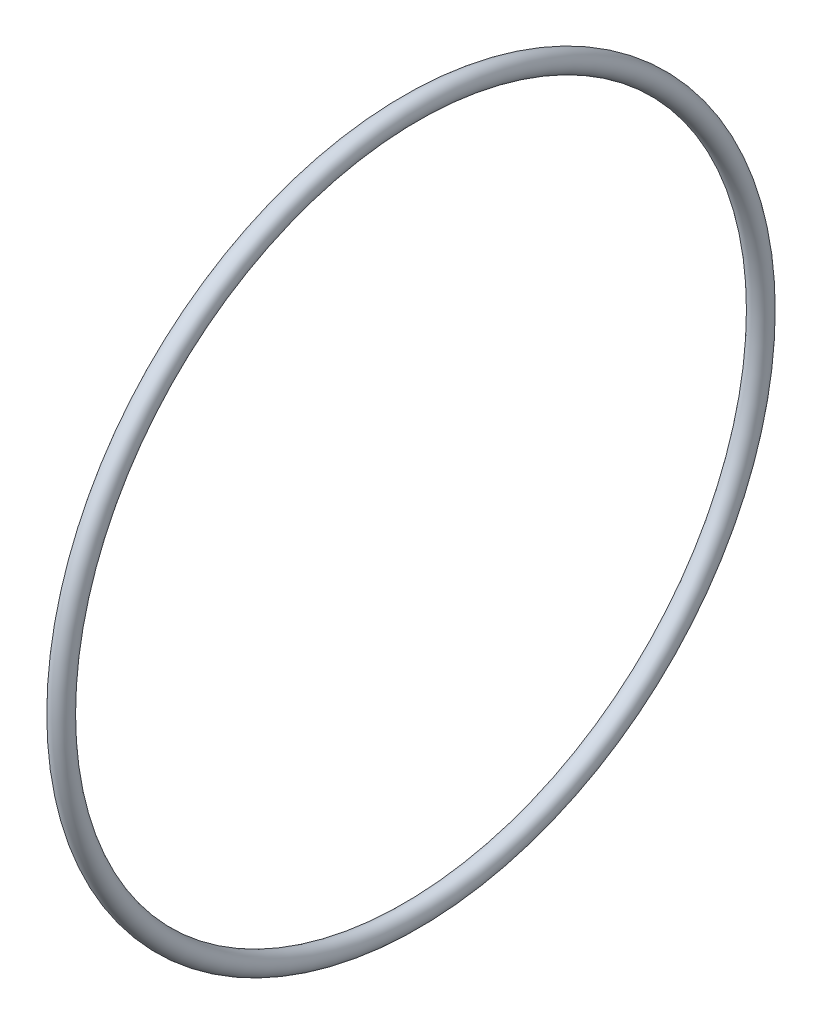
SolidWorks part; units mm, degrees
ref_plane "Front Plane" through (0, 0, 0) normal (0, 0, 1) x (1, 0, 0)
ref_plane "Top Plane" through (0, 0, 0) normal (0, 1, 0) x (1, 0, 0)
ref_plane "Right Plane" through (0, 0, 0) normal (1, 0, 0) x (0, 0, -1)
sketch "Sketch2" plane through (0, 0, 0) normal (0, 0, 1) x (1, 0, 0)
  line L0 (0, 0) -> (58.591, 0) construction
  line L2 (0, 0) -> (18.4, 0)
  line L3 (0, 0) -> (0, 2.5)
  line L4 (0, 2.5) -> (18.4, 2.5)
  line L5 (18.4, 0) -> (18.4, 2.5)
  line L6 (6.0094, 2.5) -> (6.0094, 6)
  line L11 (6.0094, 6) -> (9.9794, 6)
  line L16 (12.9794, 6) -> (12.9794, 3)
  line L17 (12.9794, 3) -> (13.6398, 3)
  line L18 (13.6398, 3) -> (13.6398, 2.5)
  line L19 (13.6398, 2.5) -> (6.0094, 2.5)
  line L22 (13.6398, 2.5) -> (16.1198, 2.5)
  line L23 (13.6398, 2.5) -> (13.6398, 4)
  line L24 (13.6398, 4) -> (16.1198, 4)
  line L25 (16.1198, 2.5) -> (16.1198, 4)
  line L27 (6.0094, 6) -> (9.9794, 6)
  line L28 (6.0094, 6) -> (6.0094, 9)
  line L29 (6.0094, 9) -> (9.9794, 9)
  line L30 (9.9794, 6) -> (9.9794, 9)
  line L31 (6.0094, 9) -> (6.0094, 8.25)
  line L32 (6.0094, 8.25) -> (5.0094, 8.25)
  line L33 (8.6609, 22.001) -> (8.6609, 12.476) construction
  line L34 (5.0094, 12.476) -> (12.3124, 12.476)
  line L35 (9.9794, 9) -> (12.3124, 9)
  line L36 (5.0094, 7.9375) -> (1.8344, 7.9375)
  line L37 (5.0094, 8.25) -> (5.0094, 12.476)
  line L38 (5.0094, 7.9375) -> (5.0094, 13.9365)
  line L39 (5.0094, 13.9365) -> (1.8344, 13.9365)
  line L40 (1.8344, 7.9375) -> (1.8344, 13.9365)
  line L41 (5.0094, 22.001) -> (12.3124, 22.001)
  line L42 (5.0094, 22.001) -> (5.0094, 30.1625)
  line L43 (5.0094, 30.1625) -> (12.3124, 30.1625)
  line L44 (12.3124, 22.001) -> (12.3124, 30.1625)
  line L49 (16.6398, 22.001) -> (16.6398, 7.5)
  line L51 (23.0198, 7.5) -> (23.0198, 6.5)
  line L54 (16.1198, 4) -> (13.6398, 4)
  line L56 (18.0398, 7.5) -> (23.0198, 7.5)
  line L57 (13.3124, 22.001) -> (16.6398, 22.001)
  line L58 (16.1198, 3.5) -> (20.0198, 3.5)
  line L59 (29.9098, 14) -> (26.9098, 11)
  line L60 (4.0094, 31.75) -> (18.0398, 31.75)
  line L61 (18.0398, 7.5) -> (23.0198, 7.5)
  line L62 (18.0398, 7.5) -> (18.0398, 12)
  line L63 (18.0398, 12) -> (23.0198, 12)
  line L64 (23.0198, 7.5) -> (23.0198, 12)
  line L65 (18.0398, 31.75) -> (18.0398, 12)
  line L66 (23.0198, 11) -> (26.9098, 11)
  line L67 (34.8098, 23) -> (31.3098, 19.5)
  line L68 (35.8098, 31) -> (38.7998, 33.99)
  line L69 (29.9098, 14) -> (29.9098, 15)
  line L70 (29.9098, 15) -> (22.9398, 15)
  line L71 (22.9398, 15) -> (21.0398, 15)
  line L72 (18.0398, 7.5) -> (16.6398, 7.5)
  line L73 (21.0398, 15) -> (21.0398, 43)
  line L74 (19.5798, 40) -> (9.6198, 40)
  line L75 (9.6198, 40) -> (4.0094, 40)
  line L76 (21.0398, 43) -> (19.5798, 43)
  line L77 (22.9398, 15) -> (29.9098, 15)
  line L78 (22.9398, 15) -> (22.9398, 21)
  line L79 (22.9398, 21) -> (29.9098, 21)
  line L80 (29.9098, 15) -> (29.9098, 21)
  line L81 (9.6198, 40) -> (19.5798, 40)
  line L82 (9.6198, 40) -> (9.6198, 50)
  line L83 (9.6198, 50) -> (19.5798, 50)
  line L84 (19.5798, 40) -> (19.5798, 50)
  line L85 (4.0094, 40) -> (4.0094, 31.75)
  line L86 (12.9794, 3) -> (12.9794, 2.5)
  line L87 (31.3098, 19.5) -> (29.9098, 19.5)
  line L88 (21.4694, 63.5) -> (21.4694, 51.308)
  line L89 (21.4694, 63.5) -> (25.9398, 63.5)
  line L90 (25.9398, 63.5) -> (25.9398, 25)
  line L91 (27.8398, 25) -> (25.9398, 25)
  line L92 (9.6198, 48) -> (8.1598, 48)
  line L93 (8.1598, 48) -> (8.1598, 53.476)
  line L94 (8.1598, 53.476) -> (19.5798, 53.476)
  line L95 (19.5798, 53.476) -> (19.5798, 50)
  line L96 (13.8698, 63.001) -> (13.8698, 53.476) construction
  line L97 (8.1598, 63.001) -> (19.5798, 63.001)
  line L98 (8.1598, 63.001) -> (8.1598, 68.2625)
  line L99 (8.1598, 68.2625) -> (19.5798, 68.2625)
  line L100 (19.5798, 63.001) -> (19.5798, 68.2625)
  line L101 (12.9794, 6) -> (11.9794, 6)
  line L102 (8.1598, 44.825) -> (4.9848, 44.825)
  line L103 (8.1598, 44.825) -> (8.1598, 54.9365)
  line L104 (8.1598, 54.9365) -> (4.9848, 54.9365)
  line L106 (9.9794, 6) -> (10.8794, 6)
  line L107 (27.8398, 25) -> (34.8098, 25)
  line L108 (34.8098, 25) -> (34.8098, 23)
  line L109 (0, 0) -> (-2, 0)
  line L110 (0, 0) -> (0, 11)
  line L111 (27.8398, 25) -> (34.8098, 25)
  line L112 (27.8398, 25) -> (27.8398, 32.5)
  line L113 (27.8398, 32.5) -> (34.8098, 32.5)
  line L114 (34.8098, 25) -> (34.8098, 32.5)
  line L115 (35.8098, 31) -> (34.8098, 31)
  line L116 (27.8398, 32.5) -> (27.8398, 64.5)
  line L117 (20.5373, 74.025) -> (6.2023, 74.025)
  line L118 (6.2023, 74.025) -> (6.2023, 76.2)
  line L119 (38.7998, 47.29) -> (30.8398, 55.25)
  line L120 (0, 11) -> (-2, 11)
  line L121 (38.7998, 43.815) -> (30.8623, 43.815)
  line L123 (-4.8152, 69.85) -> (1.5348, 76.2)
  line L124 (38.7998, 47.29) -> (38.7998, 33.99)
  line L125 (-2, 0) -> (-2, 11)
  line L126 (38.7998, 37.465) -> (30.8623, 37.465)
  line L127 (30.8623, 43.815) -> (30.8623, 37.465)
  line L128 (6.0094, 2.5) -> (6.0094, 0)
  line L129 (-0.0152, 63.5) -> (-0.0152, 30)
  line L132 (4.9848, 63.5) -> (-0.0152, 63.5)
  line L136 (-1.8152, 30) -> (-11.7752, 30)
  line L138 (-13.7752, 25.4) -> (-2, 25.4)
  line L139 (-2, 25.4) -> (-2, 11.5)
  line L140 (27.8398, 64.5) -> (20.5373, 64.5)
  line L141 (-1.8152, 30) -> (-11.7752, 30)
  line L142 (-1.8152, 30) -> (-1.8152, 39)
  line L143 (-1.8152, 39) -> (-11.7752, 39)
  line L144 (-11.7752, 30) -> (-11.7752, 39)
  line L145 (20.5373, 64.5) -> (20.5373, 74.025)
  line L146 (-12.7752, 37) -> (-12.7752, 47.29)
  line L147 (-12.7752, 37) -> (-11.7752, 37)
  line L148 (30.8398, 55.25) -> (30.8398, 76.2)
  line L149 (11.9794, 6) -> (11.9794, 5.45)
  line L154 (-2, 11.5) -> (0.5, 11.5)
  line L155 (4.9848, 60.6197) -> (24.0348, 60.6197)
  line L160 (4.9848, 60.6197) -> (4.9848, 55.8572)
  line L161 (4.9848, 55.8572) -> (24.0348, 55.8572)
  line L166 (24.0348, 60.6197) -> (24.0348, 55.8572)
  line L167 (4.9848, 60.6197) -> (24.0348, 55.8572) construction
  line L172 (4.9848, 55.8572) -> (24.0348, 60.6197) construction
  line L173 (24.0348, 62.2072) -> (25.9398, 62.2072)
  line L174 (11.9794, 5.45) -> (10.8794, 5.45)
  line L175 (10.8794, 6) -> (10.8794, 5.45)
  line L176 (24.0348, 62.2072) -> (24.0348, 54.2697)
  line L177 (24.0348, 54.2697) -> (25.9398, 54.2697)
  line L178 (25.9398, 62.2072) -> (25.9398, 54.2697)
  line L179 (24.0348, 62.2072) -> (25.9398, 54.2697) construction
  line L180 (24.0348, 54.2697) -> (25.9398, 62.2072) construction
  line L181 (3, 19.6197) -> (15.7, 19.6197)
  line L182 (3, 19.6197) -> (3, 14.8572)
  line L183 (3, 14.8572) -> (15.7, 14.8572)
  line L184 (15.7, 19.6197) -> (15.7, 14.8572)
  line L185 (3, 19.6197) -> (15.7, 14.8572) construction
  line L186 (3, 14.8572) -> (15.7, 19.6197) construction
  line L187 (15.7, 21.2072) -> (16.6398, 21.2072)
  line L188 (15.7, 21.2072) -> (15.7, 13.2697)
  line L189 (15.7, 13.2697) -> (16.6398, 13.2697)
  line L190 (16.6398, 21.2072) -> (16.6398, 13.2697)
  line L191 (15.7, 21.2072) -> (16.6398, 13.2697) construction
  line L192 (15.7, 13.2697) -> (16.6398, 21.2072) construction
  line L193 (0.5, 11.5) -> (0.5, 6.9375)
  line L194 (0.5, 6.9375) -> (1.8344, 6.9375)
  line L195 (23.0198, 6.5) -> (20.0198, 3.5)
  line L196 (4.9848, 63.5) -> (4.9848, 54.9365)
  line L197 (3, 43.825) -> (4.9848, 43.825)
  line L198 (1.8344, 6.9375) -> (1.8344, 7.9375)
  line L199 (6.0094, 0) -> (12.9794, 0)
  line L200 (12.9794, 0) -> (12.9794, 2.5)
  line L201 (18.0398, 31.75) -> (18.0398, 35.875)
  line L202 (18.0398, 35.875) -> (21.0398, 35.875)
  line L203 (30.8398, 76.2) -> (6.2023, 76.2)
  line L204 (2.7573, 69.85) -> (7.2023, 69.85) construction
  line L205 (7.2023, 67.4688) -> (26.2523, 67.4688)
  line L206 (7.2023, 74.025) -> (7.2023, 64.5)
  line L207 (7.2023, 64.5) -> (-1.8152, 64.5)
  line L208 (-1.8152, 64.5) -> (-1.8152, 39)
  line L209 (-12.7752, 47.29) -> (-4.8152, 55.25)
  line L210 (-4.8152, 55.25) -> (-4.8152, 69.85)
  line L211 (7.2023, 67.4688) -> (7.2023, 72.2312)
  line L212 (7.2023, 72.2312) -> (26.2523, 72.2313)
  line L213 (26.2523, 67.4688) -> (26.2523, 72.2313)
  line L214 (26.2523, 73.8187) -> (30.8398, 73.8187)
  line L215 (26.2523, 73.8187) -> (26.2523, 65.8813)
  line L216 (26.2523, 65.8813) -> (30.8398, 65.8813)
  line L217 (30.8398, 73.8187) -> (30.8398, 65.8813)
  line L218 (2.7573, 72.2313) -> (24.9823, 72.2313)
  line L219 (2.7573, 72.2313) -> (2.7573, 67.4687)
  line L220 (2.7573, 67.4687) -> (24.9823, 67.4687)
  line L221 (24.9823, 72.2313) -> (24.9823, 67.4687)
  line L222 (24.9823, 69.85) -> (20.5373, 69.85) construction
  line L223 (21.4694, 51.308) -> (22.9398, 51.308)
  line L224 (22.9398, 51.308) -> (22.9398, 21)
  line L225 (13.6398, 4) -> (13.6398, 12.2697)
  line L226 (13.6398, 12.2697) -> (13.3124, 12.2697)
  line L227 (13.3124, 12.2697) -> (13.3124, 22.001)
  line L228 (12.3124, 9) -> (12.3124, 12.476)
  line L229 (-1.8152, 30) -> (-0.0152, 30)
  line L230 (8.1598, 65.6317) -> (2.7573, 65.6317) construction
  line L231 (19.5798, 65.6317) -> (24.9823, 65.6317) construction
  line L232 (1.5348, 76.2) -> (6.2023, 76.2)
  line L233 (-11.7752, 30) -> (-13.7752, 30)
  line L234 (-13.7752, 30) -> (-13.7752, 25.4)
  line L235 (3, 13.9365) -> (3, 43.825)
  line L236 (4.9848, 54.9365) -> (4.9848, 44.825)
  line L237 (4.9848, 43.825) -> (4.9848, 44.825)
  circle A0 centre (26.8898, 25.95) radius 0.95
  circle A1 centre (21.9898, 15.95) radius 0.95
  circle A2 centre (17.3398, 8.2) radius 0.7
  circle A3 centre (10.4294, 6.45) radius 0.45
  circle A4 centre (-0.9152, 30.9) radius 0.9
  point P7 (24.9873, 58.2385)
  point P131 (16.1699, 17.2385)
  point P135 (14.5098, 58.2385)
  point P146 (9.35, 17.2385)
sketch "Sketch3" plane through (0, 0, 0) normal (0, 0, 1) x (1, 0, 0)
  circle A0 centre (-0.9152, 30.9) radius 0.9 construction
  circle A1 centre (-0.9152, 30.9) radius 0.9
revolve "Revolve1" add sketch "Sketch3" angle 360 about L0
